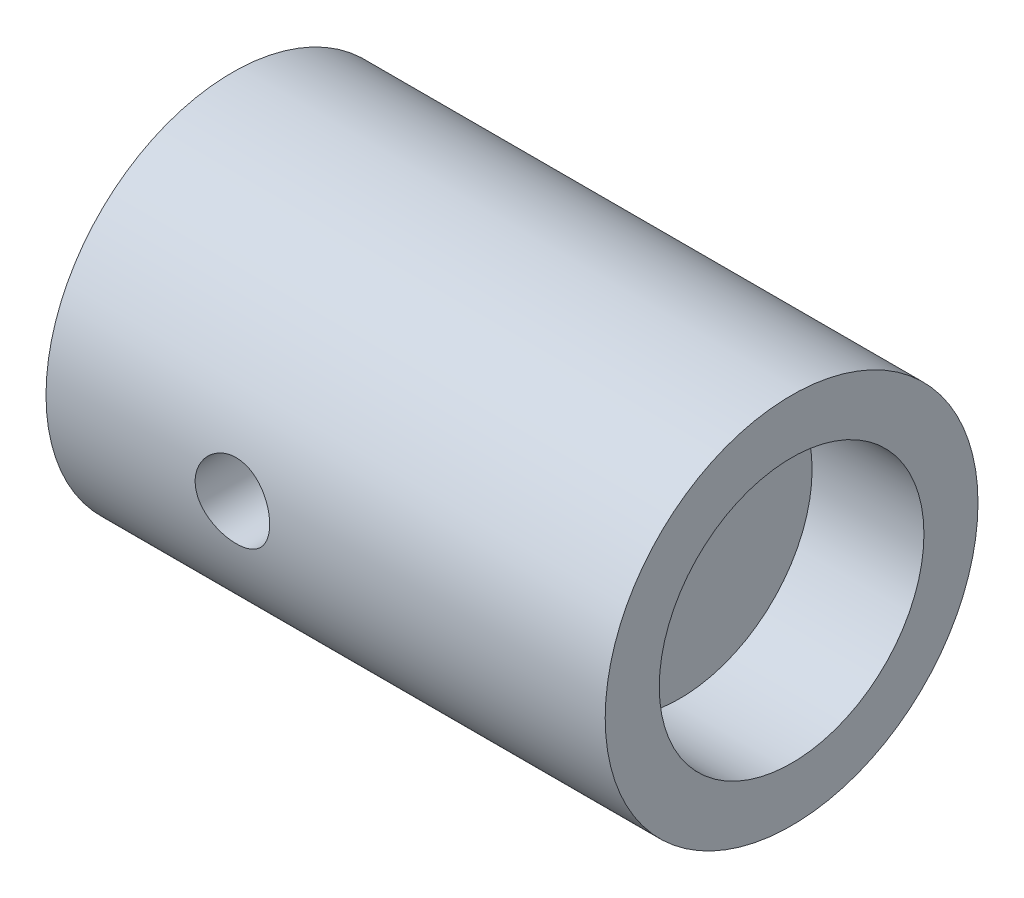
SolidWorks part; units mm, degrees
ref_plane "前视基准面" through (0, 0, 0) normal (0, 0, 1) x (1, 0, 0)
ref_plane "上视基准面" through (0, 0, 0) normal (0, 1, 0) x (1, 0, 0)
ref_plane "右视基准面" through (0, 0, 0) normal (1, 0, 0) x (0, 0, -1)
other "Configuration Table"
sketch "草图1" plane through (0, 0, 0) normal (1, 0, 0) x (0, 0, -1)
  circle A0 centre (0, 0) radius 5
  dimension "D1" = 10
extrude "凸台-拉伸1" add sketch "草图1" along normal blind 15
sketch "草图2" plane through (15, 0, 0) normal (1, 0, 0) x (0, 0, -1)
  circle A0 centre (0, 0) radius 3.55
  dimension "D1" = 7.1
extrude "切除-拉伸1" cut sketch "草图2" against normal blind 3
sketch "草图3" plane through (0, 0, 0) normal (-1, 0, 0) x (0, 0, 1)
  circle A0 centre (0, 0) radius 3
  dimension "D1" = 6
extrude "切除-拉伸2" cut sketch "草图3" against normal blind 10
sketch "草图4" plane through (0, 0, 0) normal (0, 0, 1) x (1, 0, 0)
  line L0 (0, 0) -> (15, 0) construction
  line L1 (15, -5) -> (15, 5) construction
  line L2 (0, 5) -> (0, -5) construction
  circle A0 centre (5, 0) radius 1
  dimension "D2" = 2
  dimension "D1" = 5
extrude "切除-拉伸3" cut sketch "草图4" against normal blind 5 and the other way blind 5
